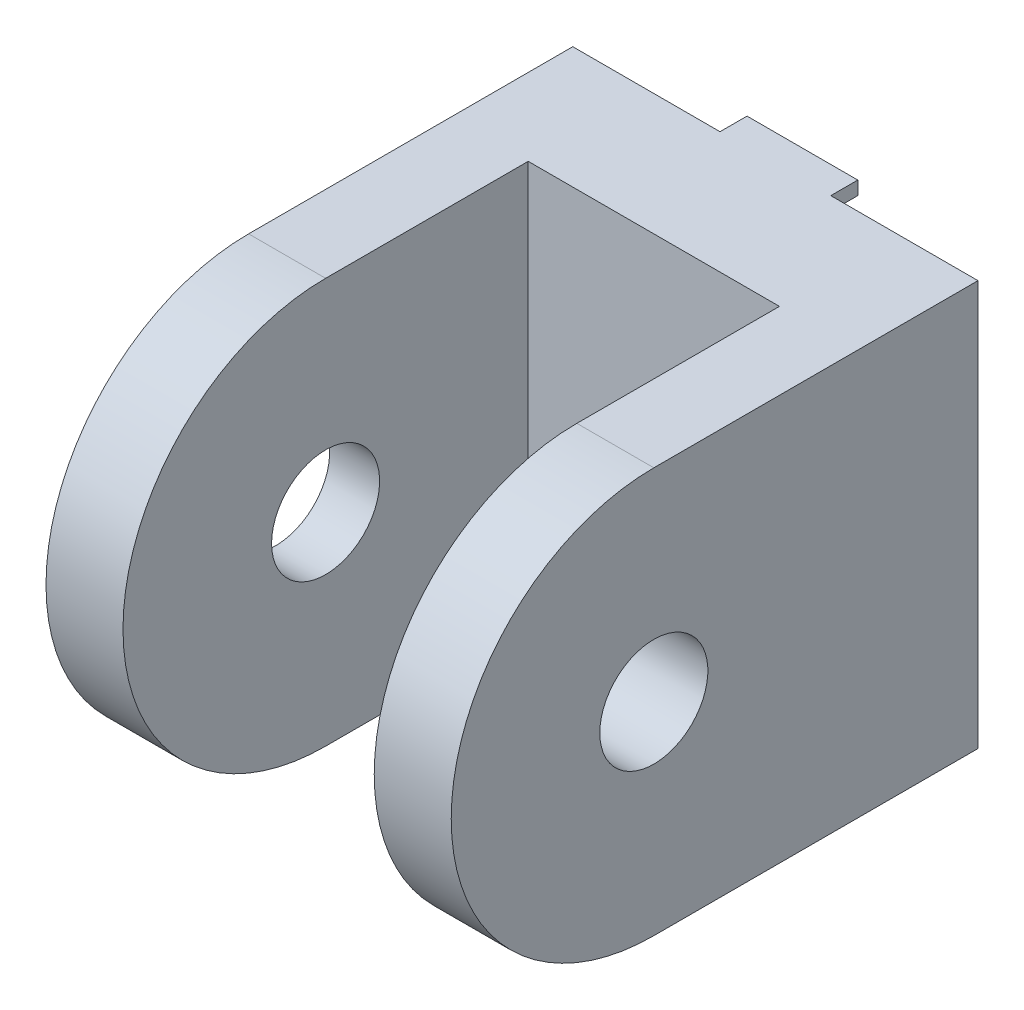
SolidWorks part; units mm, degrees
ref_plane "前视基准面" through (0, 0, 0) normal (0, 0, 1) x (1, 0, 0)
ref_plane "上视基准面" through (0, 0, 0) normal (0, 1, 0) x (1, 0, 0)
ref_plane "右视基准面" through (0, 0, 0) normal (1, 0, 0) x (0, 0, -1)
sketch "草图1" plane through (0, 0, 0) normal (0, 0, 1) x (1, 0, 0)
  line L1 (-15, -15) -> (15, -15)
  line L2 (-15, -15) -> (-15, 15)
  line L3 (-15, 15) -> (15, 15)
  line L4 (15, -15) -> (15, 15)
  line L5 (-15, -15) -> (15, 15) construction
  line L6 (-15, 15) -> (15, -15) construction
  point P0 (0, 0)
  dimension "D1" = 30
  dimension "D2" = 30
extrude "凸台-拉伸1" add sketch "草图1" along normal blind 9
sketch "草图2" plane through (0, 0, 9) normal (0, 0, 1) x (1, 0, 0)
  line L0 (15, 15) -> (-15, 15) construction
  line L1 (-15, -15) -> (-9.3, -15)
  line L2 (-15, -15) -> (-15, 15)
  line L3 (-15, 15) -> (-9.3, 15)
  line L4 (-9.3, -15) -> (-9.3, 15)
  line L5 (0, 0) -> (0, 12.8397) construction
  line L6 (15, -15) -> (9.3, -15)
  line L7 (15, -15) -> (15, 15)
  line L8 (9.3, -15) -> (9.3, 15)
  line L9 (15, 15) -> (9.3, 15)
  dimension "D1" = 5.7
extrude "凸台-拉伸2" add sketch "草图2" along normal blind 30
sketch "草图3" plane through (-15, 0, 0) normal (-1, 0, 0) x (0, 0, 1)
  line L0 (39, 15) -> (39, -15) construction
  line L1 (39, 15) -> (0, 15) construction
  line L2 (24, -15) -> (24, 15) construction
  arc A0 (24, -15) -> (24, 15) centre (24, 0) ccw
  dimension "D1" = 30
extrude "切除-拉伸2" cut sketch "草图3" against normal through all and the other way through all flip side to cut
sketch "草图4" plane through (-15, 0, 0) normal (-1, 0, 0) x (0, 0, 1)
  circle A0 centre (24, 0) radius 4
  dimension "D1" = 8
extrude "切除-拉伸3" cut sketch "草图4" against normal through all
sketch "草图5" plane through (-15, 0, 0) normal (-1, 0, 0) x (0, 0, 1)
  circle A0 centre (24, 0) radius 8
  dimension "D1" = 16
extrude "切除-拉伸4" cut sketch "草图5" against normal blind 2
sketch "草图6" plane through (0, 0, 9) normal (0, 0, 1) x (1, 0, 0)
  circle A0 centre (0, 0) radius 4
  dimension "D1" = 8
extrude "切除-拉伸5" cut sketch "草图6" against normal through all
sketch "草图7" plane through (0, 0, 0) normal (0, 0, -1) x (-1, 0, 0)
  line L0 (-15, 15) -> (15, 15) construction
  line L1 (-4.1, 15) -> (4.1, 15)
  line L2 (-4.1, 15) -> (-4.1, 14)
  line L3 (-4.1, 14) -> (4.1, 14)
  line L4 (4.1, 15) -> (4.1, 14)
  line L5 (0, 0) -> (-9.0525, 0) construction
  line L6 (4.1, -15) -> (4.1, -14)
  line L7 (-4.1, -15) -> (-4.1, -14)
  line L8 (-4.1, -14) -> (4.1, -14)
  line L9 (-4.1, -15) -> (4.1, -15)
  point P9 (0, 15)
  point P10 (0, 15)
  dimension "D1" = 8.2
  dimension "D2" = 1
extrude "凸台-拉伸3" add sketch "草图7" along normal blind 2
